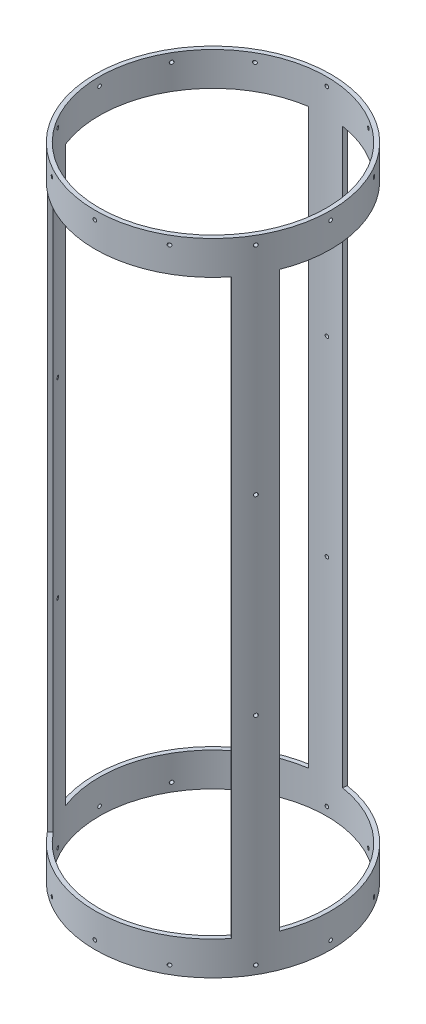
SolidWorks part; units mm, degrees
material "6061-T6 (SS)"
ref_plane "Front Plane" through (0, 0, 0) normal (0, 0, 1) x (1, 0, 0)
ref_plane "Top Plane" through (0, 0, 0) normal (0, 1, 0) x (1, 0, 0)
ref_plane "Right Plane" through (0, 0, 0) normal (1, 0, 0) x (0, 0, -1)
sketch "Sketch1" plane through (0, 0, 0) normal (0, 1, 0) x (1, 0, 0)
  circle A0 centre (0, 0) radius 88.9
  circle A1 centre (0, 0) radius 85.725
  dimension "D1" = 177.8
  dimension "D2" = 171.45
extrude "Boss-Extrude1" add sketch "Sketch1" along normal mid plane 482.854
sketch "Sketch6" plane through (0, -241.427, 0) normal (0, -1, 0) x (-1, 0, 0)
  line L0 (82.7901, -32.3885) -> (79.8333, -31.2317)
  line L1 (13.1222, 87.9262) -> (12.6536, 84.786)
  line L2 (0, 0) -> (0, 85.725) construction
  line L3 (-97.8543, 0) -> (97.8543, 0) construction
  line L4 (0, 0) -> (12.6536, 84.786) construction
  arc A0 (13.1222, 87.9262) -> (82.7901, -32.3885) centre (0, 0) cw
  circle A1 centre (0, 0) radius 88.9 construction
  arc A2 (12.6536, 84.786) -> (79.8333, -31.2317) centre (0, 0) cw
  circle A3 centre (0, 0) radius 85.725 construction
  arc A4 (0, 85.725) -> (12.6536, 84.786) centre (0, 0) cw construction
  dimension "D1" = 153.924
  dimension "D2" = 12.7
extrude "Cut-Extrude5" cut sketch "Sketch6" against normal offset from surface (432.054 mm away) 25.4 from offset 25.4 up to face at (0, 241.427, 88.9) offset against normal yes
pattern_circular "CirPattern5" count 3 over 360 about axis through (0, -241.427, 0) along (0, 1, 0) of "Cut-Extrude5"
ref_plane "Plane1" through (0, 0, -88.9) normal (0, 0, -1) x (-1, 0, 0)
sketch "Sketch3" plane through (0, 0, 0) normal (0, 0, -1) x (-1, 0, 0)
  line L1 (-88.9, -241.427) -> (88.9, -241.427) construction
  line L3 (-12.8692, 216.027) -> (-12.8692, -216.027) construction
  circle A0 centre (-0.1692, -235.077) radius 1.3525
  dimension "D1" = 6.35
  dimension "D2" = 2.7051
  dimension "D4" = 12.7
extrude "Cut-Extrude2" cut sketch "Sketch3" along normal up to surface (88.8921 mm away) up to face at (-0.0918, 0, 72.1578)
pattern_circular "CirPattern2" count 12 over 360 about axis through (0, 241.427, 0) along (0, -1, 0) of "Cut-Extrude2" reverse direction yes
sketch "Sketch4" plane through (0, 0, -88.9) normal (0, 0, -1) x (-1, 0, 0)
  line L1 (88.9, 241.427) -> (-88.9, 241.427) construction
  circle A0 centre (-0.1692, 235.077) radius 1.3525
  dimension "D1" = 2.7051
  dimension "D2" = 6.35
extrude "Cut-Extrude3" cut sketch "Sketch4" against normal blind 15.24
pattern_circular "CirPattern3" count 12 over 360 about axis through (0, 241.427, 0) along (0, 1, 0) of "Cut-Extrude3"
ref_plane "Plane2" through (0, 0, 88.9) normal (0, 0, 1) x (1, 0, 0)
sketch "Sketch5" plane through (0, 0, 88.9) normal (0, 0, 1) x (1, 0, 0)
  line L0 (-88.9, 216.027) -> (-13.1222, 216.027) construction
  line L1 (88.9, -216.027) -> (13.3458, -216.027) construction
  circle A0 centre (0.1692, 72.009) radius 1.3526
  circle A1 centre (0.1692, -72.009) radius 1.3526
  dimension "D1" = 144.018
  dimension "D2" = 144.018
  dimension "D3" = 2.7051
  dimension "D4" = 2.7051
extrude "Cut-Extrude4" cut sketch "Sketch5" against normal up to surface (177.787 mm away) up to face at (-77.2806, 234.4708, -43.9383)
pattern_circular "CirPattern4" count 3 over 360 about axis through (0, 241.427, 0) along (0, -1, 0) of "Cut-Extrude4"
